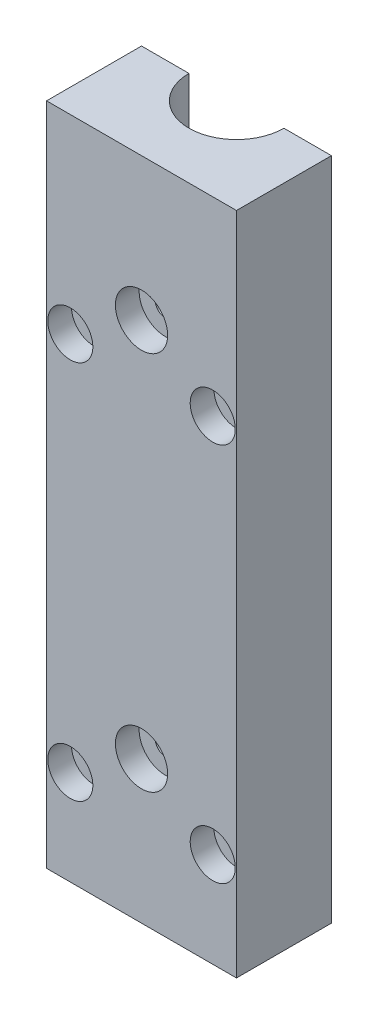
SolidWorks part; units mm, degrees
ref_plane "Front Plane" through (0, 0, 0) normal (0, 0, 1) x (1, 0, 0)
ref_plane "Top Plane" through (0, 0, 0) normal (0, 1, 0) x (1, 0, 0)
ref_plane "Right Plane" through (0, 0, 0) normal (1, 0, 0) x (0, 0, -1)
sketch "Sketch3" plane through (0, 0, 0) normal (0, 0, 1) x (1, 0, 0)
  line L1 (-20, -70) -> (20, -70)
  line L2 (-20, -70) -> (-20, 70)
  line L3 (-20, 70) -> (20, 70)
  line L4 (20, -70) -> (20, 70)
  line L5 (0, 70) -> (0, -70) construction
  line L6 (-20, 0) -> (20, 0) construction
  point P0 (0, 0)
  dimension "D1" = 40
  dimension "D2" = 140
extrude "Boss-Extrude1" add sketch "Sketch3" along normal blind 20
sketch "Sketch4" plane through (0, 70, 0) normal (0, 1, 0) x (1, 0, 0)
  line L0 (20, 0) -> (-20, 0) construction
  circle A0 centre (0, 0) radius 10
  dimension "D1" = 20
extrude "Cut-Extrude1" cut sketch "Sketch4" against normal through all
sketch "Sketch6" plane through (0, 0, 20) normal (0, 0, 1) x (1, 0, 0)
  line L0 (0, 0) -> (0, 40) construction
  line L1 (0, 0) -> (0, -40) construction
  line L2 (20, 70) -> (-20, 70) construction
  line L3 (-15, 70) -> (-15, -70) construction
  line L4 (-20, -70) -> (20, -70) construction
  line L5 (15, -70) -> (15, 70) construction
  circle A0 centre (0, 40) radius 2.1
  circle A1 centre (0, -40) radius 2.1
  circle A2 centre (0, 40) radius 5.5
  circle A3 centre (0, -40) radius 5.5
  circle A4 centre (-15, 30) radius 2.1
  circle A5 centre (-15, 30) radius 4.75
  circle A6 centre (-15, -50) radius 2.1
  circle A7 centre (-15, -50) radius 4.75
  circle A8 centre (15, -50) radius 4.75
  circle A9 centre (15, -50) radius 2.1
  circle A10 centre (15, 30) radius 4.75
  circle A11 centre (15, 30) radius 2.1
  dimension "D1" = 11
  dimension "D2" = 11
  dimension "D3" = 4.2
  dimension "D4" = 4.2
  dimension "D7" = 4.2
  dimension "D11" = 9.5
  dimension "D12" = 4.2
  dimension "D13" = 9.5
  dimension "D5" = 40
  dimension "D6" = 40
  dimension "D8" = 40
  dimension "D9" = 30
  dimension "D10" = 15
  dimension "D14" = 20
extrude "Cut-Extrude10" cut sketch "Sketch6" against normal blind 5
extrude "Cut-Extrude11" cut sketch "Sketch6<2>" against normal through all contours A4 | A0 | A11 | A6 | A1 | A9
sketch "Sketch6<2>" plane through (0, 0, 20) normal (0, 0, 1) x (1, 0, 0) same geometry as "Sketch6"
